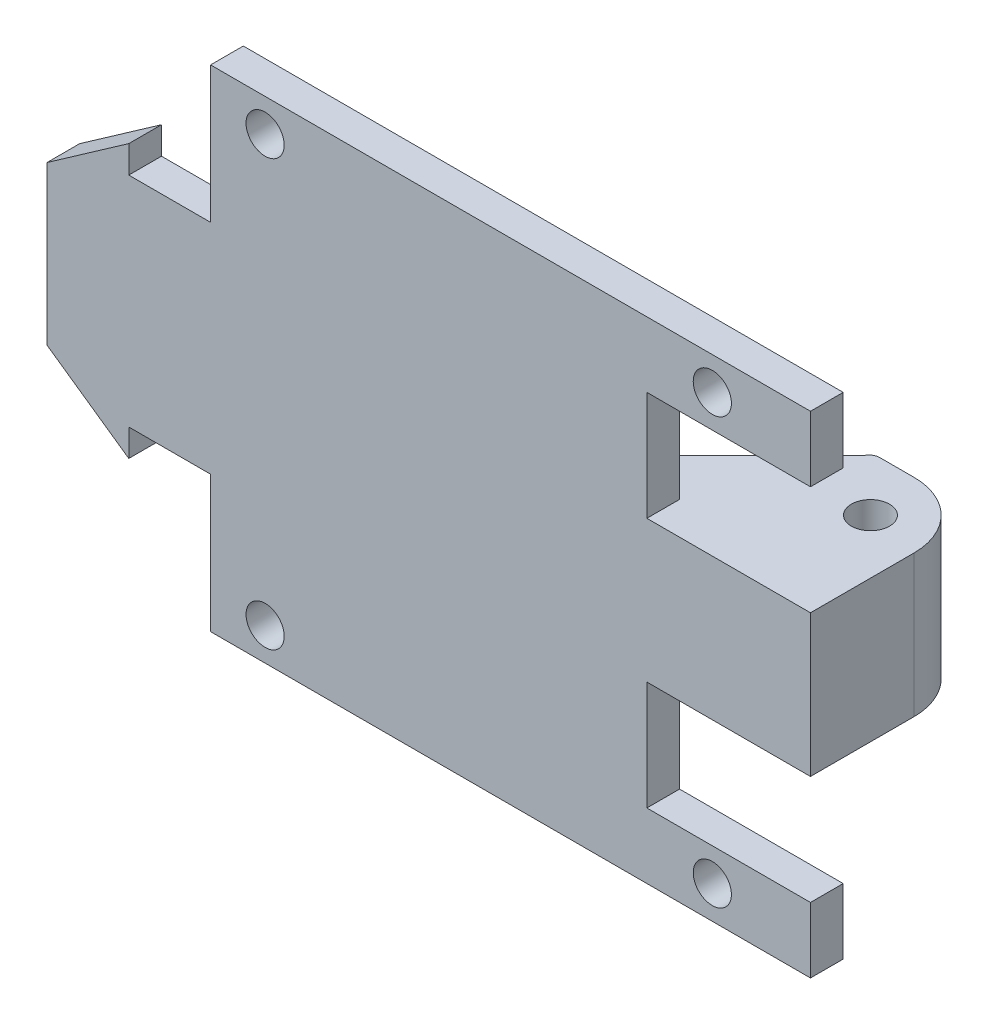
SolidWorks part; units mm, degrees
ref_plane "Front Plane" through (0, 0, 0) normal (0, 0, 1) x (1, 0, 0)
ref_plane "Top Plane" through (0, 0, 0) normal (0, 1, 0) x (1, 0, 0)
ref_plane "Right Plane" through (0, 0, 0) normal (1, 0, 0) x (0, 0, -1)
sketch "Sketch1" plane through (0, 0, 0) normal (0, 0, 1) x (1, 0, 0)
  line L0 (10.563, 19.3432) -> (10.563, -25.6568)
  line L1 (-44.437, 19.3432) -> (10.563, 19.3432)
  line L2 (-44.437, 19.3432) -> (-44.437, -25.6568)
  line L3 (-44.437, -25.6568) -> (10.563, -25.6568)
extrude "Boss-Extrude1" add sketch "Sketch1" along normal blind 3
sketch "Sketch2" plane through (0, 0, 0) normal (0, 0, -1) x (-1, 0, 0)
  line L0 (44.437, 19.3432) -> (44.437, -25.6568) construction
  line L5 (-0.563, -9.6568) -> (-10.563, -9.6568)
  line L6 (-0.563, -9.6568) -> (-0.563, 3.3432)
  line L7 (-0.563, 3.3432) -> (-10.563, 3.3432)
  line L8 (-10.563, -9.6568) -> (-10.563, 3.3432)
  line L10 (-20.563, -3.1568) -> (44.437, -3.1568) construction
  dimension "D1" = 13
  dimension "D2" = 10
  dimension "D3" = 6.5
extrude "Boss-Extrude2" add sketch "Sketch2" along normal blind 12.5
sketch "Sketch3" plane through (0, 3.3432, 0) normal (0, 1, 0) x (1, 0, 0)
  line L0 (0.563, 2.5) -> (10.563, 2.5) construction
  line L2 (0.563, 12.5) -> (0.563, 0) construction
  line L3 (10.563, 12.5) -> (10.563, 0) construction
  line L4 (0.563, 2.5) -> (10.563, 12.5) construction
  line L5 (0.563, 12.5) -> (10.563, 2.5) construction
  line L6 (0.563, 0) -> (10.563, 0) construction
  circle A0 centre (5.563, 7.5) radius 1.75
  dimension "D1" = 2.5
extrude "Cut-Extrude1" cut sketch "Sketch3" against normal blind 13.5
sketch "Sketch4" plane through (0, 0, 0) normal (0, 0, -1) x (-1, 0, 0)
  line L0 (-0.563, -9.6568) -> (-0.563, 3.3432) construction
  line L1 (4.437, 3.3432) -> (-15.563, 3.3432)
  line L2 (4.437, 3.3432) -> (4.437, 13.3432)
  line L3 (4.437, 13.3432) -> (-15.563, 13.3432)
  line L4 (-15.563, 3.3432) -> (-15.563, 13.3432)
  line L6 (-0.563, 3.3432) -> (-10.563, 3.3432) construction
  dimension "D1" = 20
  dimension "D2" = 5
  dimension "D3" = 10
  dimension "D4" = 0
fillet "Fillet1" radius 6 1 edges at (10.563, -3.1568, -12.5)
chamfer "Chamfer1" distance 12 angle 45 1 edges at (0.563, -3.1568, 0)
fillet "Fillet3" radius 1 1 edges at (0.563, -3.1568, -12.5)
ref_plane "Plane1" through (0, -3.1568, 0) normal (0, 1, 0) x (1, 0, 0)
ref_axis "Axis1" through (5.563, -9.6568, -7.5) along (0, 1, 0)
ref_plane "Plane3" through (5.563, 0, 0) normal (1, 0, 0) x (0, 0, -1)
sketch "Sketch6" plane through (5.563, 0, 0) normal (1, 0, 0) x (0, 0, -1)
  line L0 (12.5, 3.3432) -> (6.5, 3.3432) construction
  line L1 (7.5, 12.8432) -> (18, 12.8432)
  line L2 (7.5, 12.8432) -> (7.5, 7.8432)
  line L3 (7.5, 7.8432) -> (18, 7.8432)
  line L4 (18, 12.8432) -> (18, 7.8432)
  line L5 (7.5, -9.6568) -> (7.5, 3.3432) construction
  dimension "D1" = 4.5
  dimension "D2" = 5
  dimension "D3" = 10.5
  dimension "D4" = 0
extrude "Cut-Extrude3" cut sketch "Sketch4" against normal blind 5
mirror "Mirror2" about plane through (0, -3.1568, 0) normal (0, 1, 0) of "Cut-Extrude3"
sketch "Sketch7" plane through (0, 0, 0) normal (0, 0, -1) x (-1, 0, 0)
  line L0 (-1.563, -3.1568) -> (48.7662, -3.1568) construction
  line L1 (8.525, -3.1568) -> (-8.525, -3.1568) construction
  line L3 (-1.563, -3.1568) -> (-29.9947, -3.1568) construction
  line L4 (-1.563, -3.1568) -> (-1.563, 24.1217) construction
  line L5 (-1.563, -3.1568) -> (-1.563, -32.3324) construction
  line L7 (39.437, 24.1217) -> (39.437, -29.7158) construction
  line L8 (44.437, 19.3432) -> (44.437, -25.6568) construction
  line L9 (48.7662, 16.3432) -> (-29.9947, 16.3432) construction
  line L10 (-29.9947, -22.6568) -> (53.7379, -22.6568) construction
  line L11 (44.437, -25.6568) -> (-10.563, -25.6568) construction
  line L12 (-10.563, 19.3432) -> (44.437, 19.3432) construction
  line L14 (-10.563, 13.3432) -> (-10.563, 19.3432) construction
  circle A2 centre (-1.563, 16.3432) radius 1.75
  circle A3 centre (39.437, 16.3432) radius 1.75
  circle A5 centre (39.437, -22.6568) radius 1.75
  circle A6 centre (-1.563, -22.6568) radius 1.75
  dimension "D1" = 5
  dimension "D5" = 3.5
  dimension "D6" = 3.5
  dimension "D2" = 3
  dimension "D3" = 3
  dimension "D4" = 9
  dimension "D7" = 0
extrude "Cut-Extrude4" cut sketch "Sketch7" against normal blind 5
sketch "Sketch8" plane through (0, 0, 0) normal (0, 0, -1) x (-1, 0, 0)
  line L0 (44.437, 19.3432) -> (44.437, -25.6568) construction
  line L1 (44.437, 9.3432) -> (59.437, 9.3432) construction
  line L2 (44.437, 9.3432) -> (44.437, -15.6568) construction
  line L3 (44.437, -15.6568) -> (59.437, -15.6568) construction
  line L4 (59.437, 9.3432) -> (59.437, -15.6568) construction
  line L5 (-10.563, 19.3432) -> (44.437, 19.3432) construction
  line L6 (44.437, -25.6568) -> (-10.563, -25.6568) construction
  line L7 (51.937, 9.3432) -> (51.937, -15.6568) construction
  line L8 (44.437, 6.8432) -> (51.937, 6.8432)
  line L9 (44.437, -13.1568) -> (51.937, -13.1568)
  line L10 (51.937, -15.6568) -> (59.437, -10.4053)
  line L11 (51.937, 9.3432) -> (59.437, 4.0916)
  line L12 (44.437, 6.8432) -> (44.437, -13.1568)
  line L13 (51.937, 9.3432) -> (51.937, 6.8432)
  line L14 (51.937, -13.1568) -> (51.937, -15.6568)
  line L15 (59.437, 4.0916) -> (59.437, -10.4053)
  dimension "D1" = 10
  dimension "D2" = 10
  dimension "D3" = 15
  dimension "D4" = 2.5
  dimension "D5" = 2.5
  dimension "D6" = 55
  dimension "D7" = 55
extrude "Boss-Extrude4" add sketch "Sketch8" against normal blind 3 contours L11 L15 L10 L14 L9 L12 L8 L13
